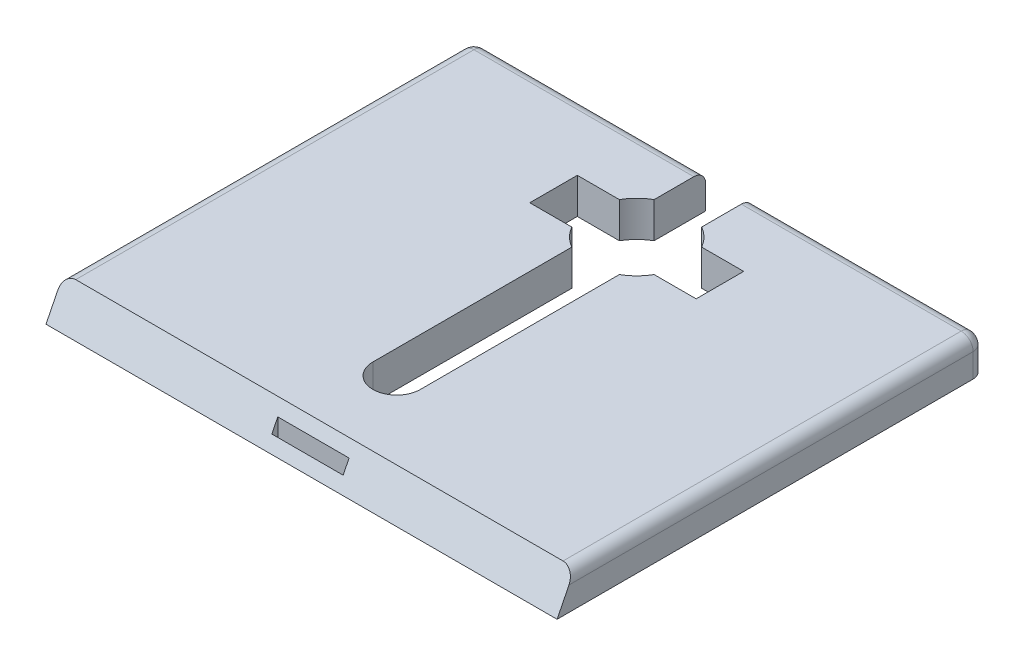
SolidWorks part; units mm, degrees
ref_plane "Ebene vorne" through (0, 0, 0) normal (0, 0, 1) x (1, 0, 0)
ref_plane "Ebene oben" through (0, 0, 0) normal (0, 1, 0) x (1, 0, 0)
ref_plane "Ebene rechts" through (0, 0, 0) normal (1, 0, 0) x (0, 0, -1)
sketch "Skizze1" plane through (0, 0, 0) normal (0, 1, 0) x (1, 0, 0)
  line L1 (-10.75, -9) -> (10.75, -9)
  line L2 (-10.75, -9) -> (-10.75, 9)
  line L3 (-10.75, 9) -> (10.75, 9)
  line L4 (10.75, -9) -> (10.75, 9)
  line L5 (-10.75, -9) -> (10.75, 9) construction
  line L6 (-10.75, 9) -> (10.75, -9) construction
  point P0 (0, 0)
  dimension "D1" = 18
  dimension "D2" = 21.5
extrude "Aufsatz-Linear austragen1" add sketch "Skizze1" along normal blind 1.5
fillet "Verrundung1" radius 0.5 3 edges at (10.75, 1.5, 0) (0, 1.5, -9) (-10.75, 1.5, 0)
sketch "Skizze2" plane through (-10.75, 0, 0) normal (-1, 0, 0) x (0, 0, 1)
  line L0 (9, 0) -> (8.25, 1.5)
  line L1 (-8.5, 1.5) -> (9, 1.5) construction
  line L2 (8.25, 1.5) -> (9, 1.5)
  line L3 (9, 1.5) -> (9, 0)
  dimension "D1" = 0.75
extrude "Schnitt-Linear austragen1" cut sketch "Skizze2" against normal up to surface (21.5 mm away) up to face at (10.75, 0.5, 0)
sketch "Skizze4" plane through (0, 1.5, 0) normal (0, 1, 0) x (1, 0, 0)
  line L6 (10.25, -8.25) -> (-10.25, -8.25) construction
  line L7 (-1.5, -8.75) -> (1.5, -8.75)
  line L8 (-1.5, -8.75) -> (-1.5, -8.5)
  line L9 (-1.5, -8.5) -> (1.5, -8.5)
  line L10 (1.5, -8.75) -> (1.5, -8.5)
  line L11 (-1.5, -8.75) -> (1.5, -8.5) construction
  line L12 (-1.5, -8.5) -> (1.5, -8.75) construction
  line L13 (-10.75, -8.5) -> (-10.75, -9) construction
  point P0 (0, -8.625)
  dimension "D1" = 0.25
  dimension "D2" = 0.25
  dimension "D3" = 3
  dimension "D4" = 10.75
extrude "Schnitt-Linear austragen2" cut sketch "Skizze4" against normal up to surface (1.5 mm away) up to face at (0, 0, 0)
fillet "Verrundung2" radius 0.5 4 edges at (10.6036, 1.3536, -8.8536) (-10.6036, 1.3536, -8.8536) (10.75, 0.5, -9) (-10.75, 0.5, -9)
sketch "Skizze5" plane through (0, 1.5, 0) normal (0, 1, 0) x (1, 0, 0)
  line L0 (-10.75, 8.5) -> (-10.75, -9) construction
  line L1 (-3.5, 4.1) -> (3.5, 4.1)
  line L2 (-3.5, 4.1) -> (-3.5, 6.1)
  line L3 (-3.5, 6.1) -> (3.5, 6.1)
  line L4 (3.5, 4.1) -> (3.5, 6.1)
  line L5 (-3.5, 4.1) -> (3.5, 6.1) construction
  line L6 (-3.5, 6.1) -> (3.5, 4.1) construction
  line L7 (-10.25, 9) -> (10.25, 9) construction
  circle A0 centre (0, 5.1) radius 2
  dimension "D2" = 4
  dimension "D1" = 7
  dimension "D3" = 2
  dimension "D4" = 10.75
  dimension "D5" = 3.9
extrude "Schlüsselloch" cut sketch "Skizze5" against normal up to surface (1.5 mm away) contours A0 L3 L2 L1 | L3 A0 | L1 A0 L3 | L1 A0 | A0 L1 L4 L3 region at (-2.7046, 1.5, -5.1) region at (0, 1.5, -5.1) region at (0, 1.5, -3.69) region at (2.7046, 1.5, -5.1) region at (0, 1.5, -6.51) up to face at (0, 0, 8.625)
sketch "Skizze6" plane through (0, 1.5, 0) normal (0, 1, 0) x (1, 0, 0)
  line L0 (0, 9) -> (0, -5) construction
  line L1 (-10.25, 9) -> (10.25, 9) construction
  line L2 (1, 9) -> (1, -5)
  line L3 (-1, 9) -> (-1, -5)
  line L5 (10.25, -8.25) -> (10.25, 8.5) construction
  arc A0 (1, 9) -> (-1, 9) centre (0, 9) ccw
  arc A1 (-1, -5) -> (1, -5) centre (0, -5) ccw
  point P4 (0, 2)
  dimension "D3" = 14
  dimension "D1" = 10.25
  dimension "D2" = 1
extrude "Langloch" cut sketch "Skizze6" against normal up to surface (1.5 mm away) up to face at (0, 0, -5.1)
